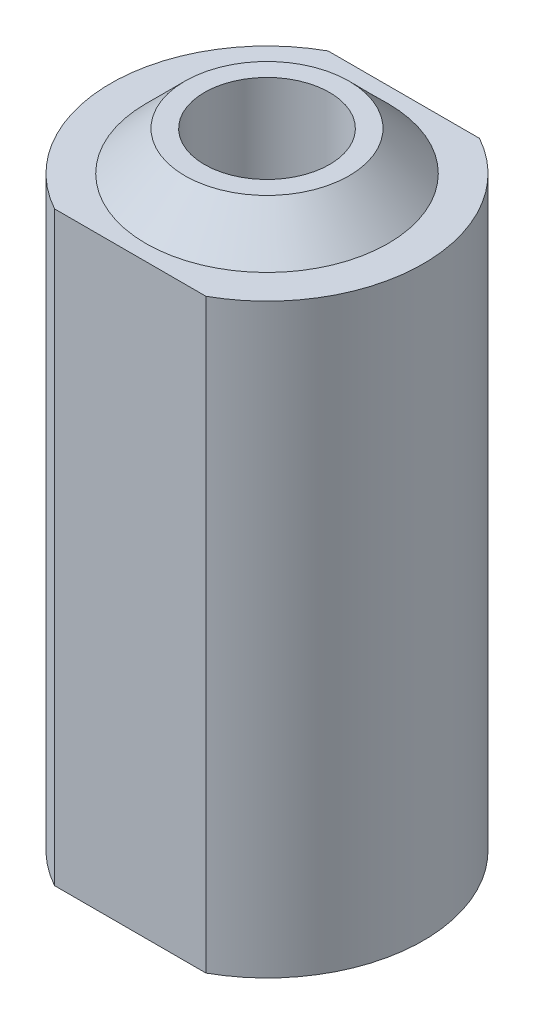
SolidWorks part; units mm, degrees
ref_plane "Front Plane" through (0, 0, 0) normal (0, 0, 1) x (1, 0, 0)
ref_plane "Top Plane" through (0, 0, 0) normal (0, 1, 0) x (1, 0, 0)
ref_plane "Right Plane" through (0, 0, 0) normal (1, 0, 0) x (0, 0, -1)
sketch "Sketch1" plane through (0, 0, 0) normal (0, 1, 0) x (1, 0, 0)
  line L0 (-1.9365, -3.5) -> (1.9365, -3.5)
  line L1 (-1.9365, 3.5) -> (1.9365, 3.5)
  line L2 (0, 3.5) -> (0, -3.5) construction
  arc A0 (-1.9365, 3.5) -> (-1.9365, -3.5) centre (0, 0) ccw
  circle A1 centre (0, 0) radius 1.6
  arc A2 (1.9365, -3.5) -> (1.9365, 3.5) centre (0, 0) ccw
  point P9 (0, 0)
  dimension "D1" = 3.2
  dimension "D2" = 8
  dimension "D3" = 7
extrude "Boss-Extrude1" add sketch "Sketch1" along normal blind 15
sketch "Sketch2" plane through (0, 15, 0) normal (0, 1, 0) x (1, 0, 0)
  circle A0 centre (0, 0) radius 3.1
  circle A1 centre (0, 0) radius 1.6 construction
  circle A2 centre (0, 0) radius 1.6
  dimension "D1" = 1.5
extrude "Boss-Extrude2" add sketch "Sketch2" along normal blind 1
chamfer "Chamfer1" distance 1 angle 45 1 edges at (0, 16, 3.1)
